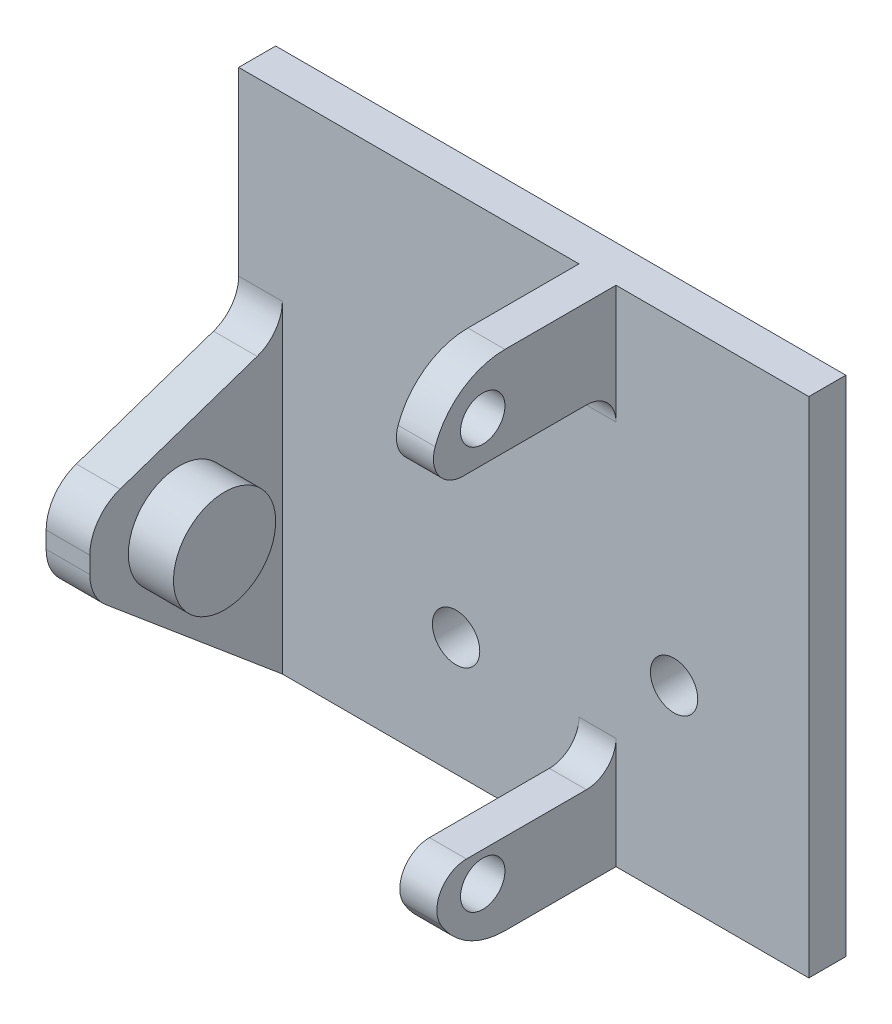
SolidWorks part; units mm, degrees
ref_plane "Plano frontal" through (0, 0, 0) normal (0, 0, 1) x (1, 0, 0)
ref_plane "Plano superior" through (0, 0, 0) normal (0, 1, 0) x (1, 0, 0)
ref_plane "Plano direito" through (0, 0, 0) normal (1, 0, 0) x (0, 0, -1)
other "Centro da massa"
sketch "Esboço1" plane through (0, 0, 0) normal (0, 0, 1) x (1, 0, 0)
  line L1 (-22.645, 6.7101) -> (15.855, 6.7101)
  line L2 (-22.645, 6.7101) -> (-22.645, -27.2899)
  line L3 (-22.645, -27.2899) -> (15.855, -27.2899)
  line L4 (15.855, 6.7101) -> (15.855, -27.2899)
  dimension "D1" = 38.5
  dimension "D2" = 34
extrude "Ressalto-extrusão1" add sketch "Esboço1" along normal blind 2.5
sketch "Esboço2" plane through (0, 0, 2.5) normal (0, 0, 1) x (1, 0, 0)
  line L0 (1.585, 6.7101) -> (1.585, -27.2899) construction
  line L1 (15.855, 6.7101) -> (-22.645, 6.7101) construction
  line L3 (0.335, 6.7101) -> (0.335, 0.7101)
  line L4 (0.335, 0.7101) -> (2.835, 0.7101)
  line L5 (2.835, 6.7101) -> (2.835, 0.7101)
  line L6 (0.335, 6.7101) -> (2.835, 6.7101)
  line L7 (-22.645, -21.7899) -> (15.855, -21.7899) construction
  line L8 (-22.645, 6.7101) -> (-22.645, -27.2899) construction
  line L9 (15.855, -27.2899) -> (15.855, 6.7101) construction
  line L28 (0.335, 6.7101) -> (0.335, -27.2899) construction
  line L29 (-22.645, -27.2899) -> (15.855, -27.2899) construction
  line L30 (2.835, 6.7101) -> (2.835, -27.2899) construction
  line L31 (0.335, -27.2899) -> (0.335, -21.7899)
  line L32 (0.335, -21.7899) -> (2.835, -21.7899)
  line L33 (2.835, -21.7899) -> (2.835, -27.2899)
  line L34 (2.835, -27.2899) -> (0.335, -27.2899)
  point P11 (1.585, 0.7101)
  dimension "D1" = 1.25
  dimension "D2" = 22.5
  dimension "D3" = 6
  dimension "D4" = 24.23
  dimension "D5" = 14.27
extrude "Ressalto-extrusão2" add sketch "Esboço2" along normal blind 12.5
sketch "Esboço3" plane through (2.835, 0, 0) normal (1, 0, 0) x (0, 0, -1)
  line L0 (-11.5, 6.7101) -> (-11.5, 0.7101) construction
  line L1 (-15, 6.7101) -> (-2.5, 6.7101) construction
  line L2 (-15, 0.7101) -> (-2.5, 0.7101) construction
  line L3 (-2.5, 0.7101) -> (-2.5, 6.7101) construction
  line L4 (-11.5, 6.7101) -> (-11.5, -27.2899) construction
  line L5 (-15, -21.7899) -> (-2.5, -21.7899) construction
  circle A0 centre (-11.5, 3.4101) radius 1.5
  circle A1 centre (-11.5, -23.7899) radius 1.5
  point P10 (-11.5, 1.9101)
  point P16 (-11.5, -25.2899)
  point P17 (-11.5, -22.2899)
  dimension "D2" = 1.2
  dimension "D3" = 2
  dimension "D1" = 9
extrude "Corte-extrusão1" cut sketch "Esboço3" against normal up to next
sketch "Esboço4" plane through (0, 0, 2.5) normal (0, 0, 1) x (1, 0, 0)
  line L0 (-19.695, 6.7101) -> (-19.695, -27.2899) construction
  line L1 (0.335, 6.7101) -> (-22.645, 6.7101) construction
  line L2 (-22.645, -27.2899) -> (0.335, -27.2899) construction
  line L3 (-22.645, 6.7101) -> (-22.645, -27.2899) construction
  line L4 (-19.695, -27.2899) -> (-19.695, -7.2899)
  line L5 (-19.695, -7.2899) -> (-22.645, -7.2899)
  line L6 (-22.645, -7.2899) -> (-22.645, -27.2899)
  line L7 (-22.645, -27.2899) -> (-19.695, -27.2899)
  point P6 (-19.695, -7.2899)
  dimension "D1" = 2.95
  dimension "D2" = 20
extrude "Ressalto-extrusão3" add sketch "Esboço4" along normal blind 13
sketch "Esboço5" plane through (-22.645, 0, 0) normal (-1, 0, 0) x (0, 0, 1)
  line L0 (2.5, -7.2899) -> (2.5, -27.2899) construction
  line L1 (2.5, -15.0899) -> (15.5, -15.0899) construction
  line L2 (15.5, -7.2899) -> (15.5, -27.2899) construction
  line L3 (15.5, -27.2899) -> (0, -27.2899) construction
  line L4 (2.5, -27.2899) -> (15.5, -16.3664)
  line L6 (15.5, -11.6895) -> (2.5, -7.2899)
  line L7 (15.222, -11.5954) -> (15.222, -16.5999)
  circle A0 centre (9.45, -15.0899) radius 3.45
  line M3 (0, -27.2899) -> (15.5, -27.2899)
  line M4 (15.5, -27.2899) -> (15.5, -7.2899)
  line M5 (15.5, -7.2899) -> (2.5, -7.2899)
  dimension "D2" = 6.95
  dimension "D1" = 12.2
extrude "Corte-extrusão2" cut sketch "Esboço5" against normal blind 15 contours L6 M4 M5 | L4 M3 M4 | A0 region at (-22.645, -23.6487, 11.1667) region at (-22.645, -8.7564, 11.1667) region at (-22.645, -15.0899, 9.45)
fillet "Filete1" radius 3 2 edges at (-21.17, -16.3664, 15.5) (-21.17, -11.6895, 15.5)
fillet "Filete2" radius 2.5 1 edges at (-21.17, -7.2899, 2.5)
sketch "Esboço6" plane through (-19.695, 0, 0) normal (1, 0, 0) x (0, 0, -1)
  circle A0 centre (-9.45, -15.0899) radius 3.45
sketch "Esboço7" plane through (-22.645, 0, 0) normal (-1, 0, 0) x (0, 0, 1)
  circle A0 centre (9.45, -15.0899) radius 3.45
extrude "Ressalto-extrusão5" add sketch "Esboço7" against normal blind 6
sketch "Esboço8" plane through (0, 0, 0) normal (0, 0, -1) x (-1, 0, 0)
  line L0 (7.965, 6.7101) -> (7.965, -27.2899) construction
  line L1 (-15.855, 6.7101) -> (22.645, 6.7101) construction
  line L2 (22.645, -27.2899) -> (-15.855, -27.2899) construction
  line L3 (22.645, 6.7101) -> (22.645, -27.2899) construction
  line L4 (7.965, -19.2899) -> (22.645, -19.2899) construction
  line L6 (-6.755, 6.7101) -> (-6.755, -27.2899) construction
  line L7 (-15.855, -27.2899) -> (-15.855, 6.7101) construction
  line L8 (-15.855, -14.7399) -> (-6.755, -14.7399) construction
  circle A1 centre (7.965, -19.2899) radius 1.6
  circle A2 centre (-6.755, -14.7399) radius 1.6
  dimension "D3" = 3.2
  dimension "D4" = 9.1
  dimension "D6" = 3.2
  dimension "D1" = 14.68
  dimension "D2" = 8
  dimension "D5" = 12.55
extrude "Corte-extrusão3" cut sketch "Esboço8" against normal blind 6
fillet "Filete3" radius 2 2 edges at (1.585, -21.7899, 2.5) (1.585, 0.7101, 2.5)
fillet "Filete4" radius 5 2 edges at (1.585, -27.2899, 15) (1.585, 6.7101, 15)
fillet "Filete5" radius 2 2 edges at (1.585, 0.7101, 15) (1.585, -21.7899, 15)
